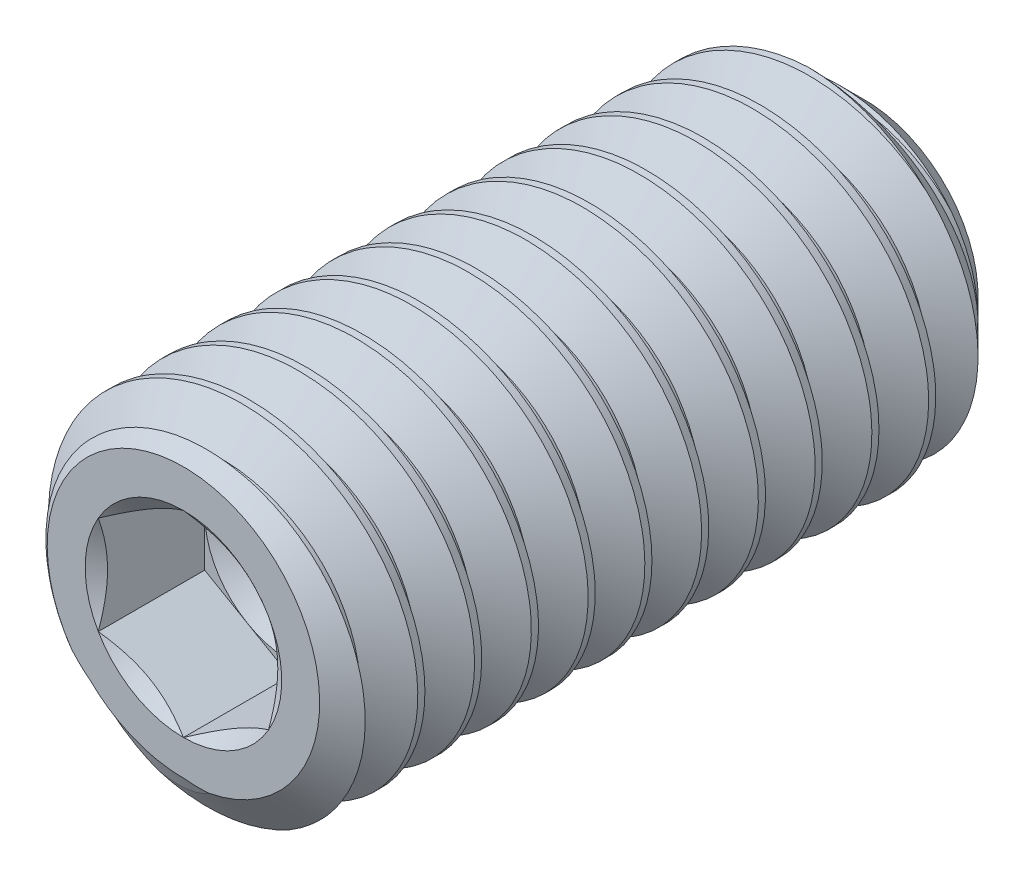
SolidWorks part; units mm, degrees
ref_plane "Front" through (0, 0, 0) normal (0, 0, 1) x (1, 0, 0)
ref_plane "Top" through (0, 0, 0) normal (0, 1, 0) x (1, 0, 0)
ref_plane "Right" through (0, 0, 0) normal (1, 0, 0) x (0, 0, -1)
sketch "Sketch22" plane through (0, 0, 0) normal (1, 0, 0) x (0, 0, -1)
  line L0 (-3, 0) -> (-3, 1.2)
  line L1 (-3, 1.2) -> (-2.7899, 1.5)
  line L2 (-2.7899, 1.5) -> (2.5, 1.5)
  line L3 (2.5, 1.5) -> (3, 1)
  line L4 (-0.145, 1.5) -> (-0.145, -1.5) construction
  line L5 (3, 0) -> (-3, 0)
  line L6 (-3, 1.2) -> (-3, -1.2) construction
  line L7 (3, 0) -> (3, 1)
  point P11 (-0.145, 0)
  dimension "Length" = 6
  dimension "D3" = 35
  dimension "D6" = 45
  dimension "Dia" = 3
  dimension "D1" = 2.4
  dimension "D2" = 0.5
revolve "Revolve1" add sketch "Sketch22" angle 360 about L5
ref_plane "Plane1" through (0, 0, -3) normal (0, 0, 1) x (1, 0, 0)
sketch "Sketch23" plane through (0, 0, 3) normal (0, 0, 1) x (1, 0, 0)
  line L1 (0, 0.866) -> (-0.75, 0.433)
  line L2 (-0.75, 0.433) -> (-0.75, -0.433)
  line L3 (-0.75, -0.433) -> (0, -0.866)
  line L4 (0, -0.866) -> (0.75, -0.433)
  line L5 (0.75, -0.433) -> (0.75, 0.433)
  line L6 (0.75, 0.433) -> (0, 0.866)
  circle A0 centre (0, 0) radius 0.75 construction
  dimension "Hex" = 1.5
extrude "Cut-Extrude10" cut sketch "Sketch23" against normal blind 0.9375
sketch "Sketch24" plane through (0, 0, 3) normal (0, 0, 1) x (1, 0, 0)
  circle A0 centre (0, 0) radius 0.866
extrude "Cut-Extrude11" cut sketch "Sketch24" against normal through all draft 55
sketch "Sketch26" plane through (0, 0, 2.0625) normal (0, 0, 1) x (1, 0, 0)
  circle A0 centre (0, 0) radius 0.75 construction
  circle A1 centre (0, 0) radius 0.75
extrude "Cut-Extrude12" cut sketch "Sketch26" against normal through all draft 60
sketch "Sketch30" plane through (0, 0, 0) normal (1, 0, 0) x (0, 0, -1)
  line L0 (-2.7899, 1.5) -> (2.5, 1.5) construction
  line L1 (-3, 0) -> (-3, 1.2) construction
  line L2 (3, 0) -> (3, 1) construction
  point P0 (-3, 1.5)
  point P1 (3, 1.5)
  point P2 (3, -1.5)
  point P11 (1.75, -1.5)
  dimension "D1" = 1.25
sketch "Sketch27" plane through (0, 0, -3) normal (0, 0, 1) x (1, 0, 0)
  circle A0 centre (0, 0) radius 1.5 construction
  circle A1 centre (0, 0) radius 1.5
curve "Helix/Spiral1" pitch 0.5 height 6.5 radius 1.5 centre (0, 0, -3) axis (0, 0, 1) start towards (0, 1, 0)
sketch "Sketch28" plane through (0, 0, 0) normal (1, 0, 0) x (0, 0, -1)
  line L0 (3, 1.5) -> (3.4375, 1.5)
  line L1 (3.4375, 1.5) -> (3.25, 1.1752)
  line L2 (3.25, 1.1752) -> (3.1875, 1.1752)
  line L3 (3.1875, 1.1752) -> (3, 1.5)
  line L4 (3.0937, 1.3376) -> (3.3437, 1.3376) construction
  line L6 (-2.7899, 1.5) -> (2.5, 1.5) construction
  dimension "D1" = 0.0625
  dimension "D3" = 60
  dimension "D2" = 0.25
sweep "Cut-Sweep2" cut profiles "Sketch28" path "Helix/Spiral1"
ref_plane "Contact Plane 1" through (0, 0, 3) normal (0, 0, 1) x (1, 0, 0)
ref_plane "Contact Plane 2" through (0, 0, -3) normal (0, 0, -1) x (-1, 0, 0)
ref_axis "Center Axis 1" through (0, 0, -3) along (0, 0, 1)
equation "\"D1@Sketch28\" = \"D4@Helix/Spiral1\" * .125"
equation "\"D2@Sketch28\" = \"D4@Helix/Spiral1\" * .5"
equation "\"D3@Helix/Spiral1\" = \"Length@Sketch22\" + \"D4@Helix/Spiral1\""
equation "\"D1@Sketch30\" = \"D4@Helix/Spiral1\" * 2.5"
equation "\"hex Depth@Cut-Extrude10\" = \"Hex@Sketch23\" * .625"
equation "\"D1@Sketch22\" = \"Dia@Sketch22\" * .8"
equation "\"D2@Sketch22\" = \"D4@Helix/Spiral1\""
